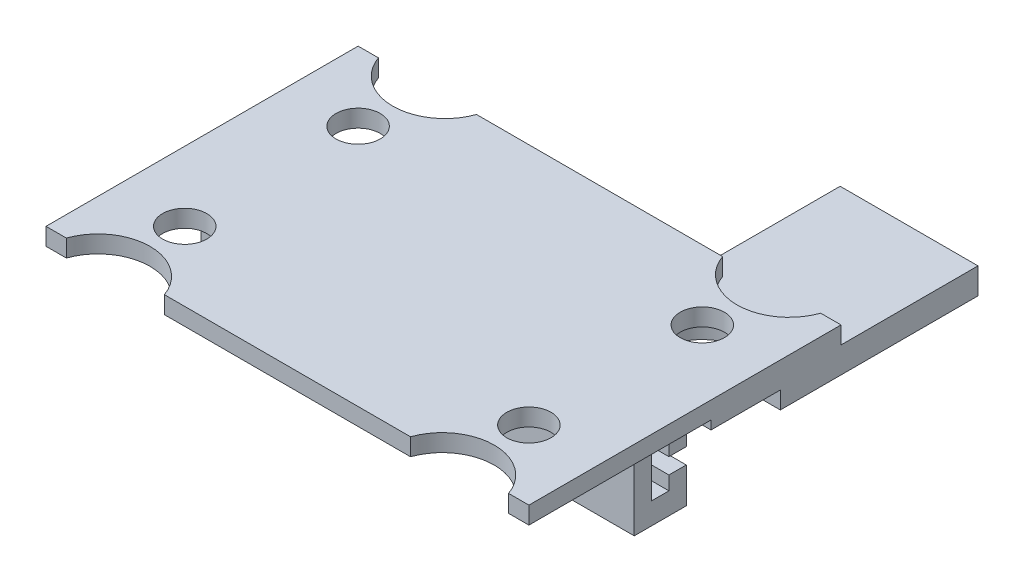
SolidWorks part; units mm, degrees
ref_plane "Front Plane" through (0, 0, 0) normal (0, 0, 1) x (1, 0, 0)
ref_plane "Top Plane" through (0, 0, 0) normal (0, 1, 0) x (1, 0, 0)
ref_plane "Right Plane" through (0, 0, 0) normal (1, 0, 0) x (0, 0, -1)
sketch "Sketch1" plane through (0, 0, 0) normal (1, 0, 0) x (0, 0, -1)
  line L0 (0, 0) -> (6.25, 0)
  line L2 (4, 2.5) -> (2, 2.5)
  line L3 (2, 2.5) -> (2, 7.5)
  line L4 (2, 7.5) -> (4, 7.5)
  line L6 (6.25, 10) -> (0, 10)
  line L7 (0, 10) -> (0, 0)
  line L8 (4, 7.5) -> (4, 5.9125)
  line L9 (4, 5.9125) -> (6, 5.9125)
  line L10 (6, 5.9125) -> (6, 10)
  line L11 (6, 10) -> (6.25, 10)
  line L12 (4, 2.5) -> (4, 4.0875)
  line L13 (4, 4.0875) -> (6, 4.0875)
  line L14 (6, 4.0875) -> (6, 0)
  line L15 (6, 0) -> (6.25, 0)
  dimension "D1" = 5
  dimension "D2" = 1.5875
  dimension "D3" = 2
  dimension "D4" = 2
  dimension "D5" = 2
  dimension "D6" = 10
extrude "Boss-Extrude1" add sketch "Sketch1" along normal blind 50 contours L14 L13 L12 L2 L3 L4 L8 L9 L10 L6 L7 L0 region at (0, 5, -0.1166)
sketch "Sketch2" plane through (0, 10, 0) normal (0, 1, 0) x (1, 0, 0)
  line L1 (-2.85, -15) -> (52.85, -15)
  line L2 (-2.85, -15) -> (-2.85, 21)
  line L3 (-2.85, 21) -> (52.85, 21)
  line L4 (52.85, -15) -> (52.85, 21)
  line L5 (0, 3) -> (50, 3) construction
  line L6 (0, 6) -> (0, 0) construction
  line L7 (50, 6) -> (50, 0) construction
  line L8 (-2.85, 3) -> (52.85, 3) construction
  line L9 (25, 21) -> (25, -15) construction
  line L10 (25, 6) -> (25, 0) construction
  line L11 (50, 6) -> (0, 6) construction
  line L12 (50, 0) -> (0, 0) construction
  line L13 (5.15, -7) -> (44.85, -7) construction
  line L14 (5.15, 13) -> (44.85, 13) construction
  circle A0 centre (5.15, 13) radius 2.55
  circle A1 centre (44.85, 13) radius 2.55
  circle A2 centre (44.85, -7) radius 2.55
  circle A3 centre (5.15, -7) radius 2.55
  dimension "D1" = 5.1
  dimension "D2" = 39.7
  dimension "D3" = 20
  dimension "D4" = 39.7
  dimension "D5" = 8
  dimension "D6" = 8
  dimension "D7" = 8
extrude "Boss-Extrude2" add sketch "Sketch2" along normal blind 2
sketch "Sketch13" plane through (0, 10, 0) normal (0, -1, 0) x (1, 0, 0)
  line L0 (44.85, -13) -> (44.85, 7) construction
  line L1 (5.15, -13) -> (5.15, 7) construction
  circle A0 centre (44.85, -23) radius 6
  circle A1 centre (44.85, 17) radius 6
  circle A2 centre (5.15, 17) radius 6
  circle A3 centre (5.15, -23) radius 6
  dimension "D2" = 12
  dimension "D1" = 10
  dimension "D3" = 10
  dimension "D4" = 10
  dimension "D5" = 10
extrude "Cut-Extrude4" cut sketch "Sketch13" against normal up to surface (2 mm away) contours A2 | A1 | A0 | A3 up to face at (25, 12, -3)
sketch "Sketch14" plane through (0, 10, 0) normal (0, -1, 0) x (1, 0, 0)
  line L5 (52.85, 15) -> (52.85, -21) construction
  line L18 (50, -6) -> (0, -6) construction
  line L19 (36.95, -6) -> (52.85, -6)
  line L20 (36.95, -6) -> (36.95, -36.8)
  line L21 (36.95, -36.8) -> (52.85, -36.8)
  line L22 (52.85, -6) -> (52.85, -36.8)
  circle A8 centre (44.85, -13) radius 2.55 construction
  circle A9 centre (44.85, -13) radius 2.55
  circle A10 centre (44.85, -13) radius 5
  line M10 (10.8069, -21) -> (39.1931, -21)
  arc M11 (39.1931, -21) -> (50.5069, -21) centre (44.85, -23) cw
  line M12 (50.5069, -21) -> (52.85, -21)
  line M13 (52.85, -21) -> (52.85, 15)
  line M41 (50, -6) -> (0, -6)
  dimension "D6" = 10
  dimension "D4" = 15.9
  dimension "D5" = 30.8
extrude "Boss-Extrude4" add sketch "Sketch14" along normal blind 3 contours A10 L19 L20 M11 M12 M13 M41 M10 | A10 L20 L21 L22 M11 M10 M12 region at (43.475, 10, -6.2186) region at (44.8947, 10, -27.9028)
sketch "Sketch15" plane through (0, 7, 0) normal (0, -1, 0) x (1, 0, 0)
  line L0 (52.85, -36.8) -> (52.85, -6) construction
  line L1 (36.95, -6) -> (52.85, -6)
  line L2 (36.95, -6) -> (36.95, -14)
  line L3 (36.95, -14) -> (52.85, -14)
  line L4 (52.85, -6) -> (52.85, -14)
  dimension "D1" = 8
extrude "Cut-Extrude5" cut sketch "Sketch15" against normal blind 2
